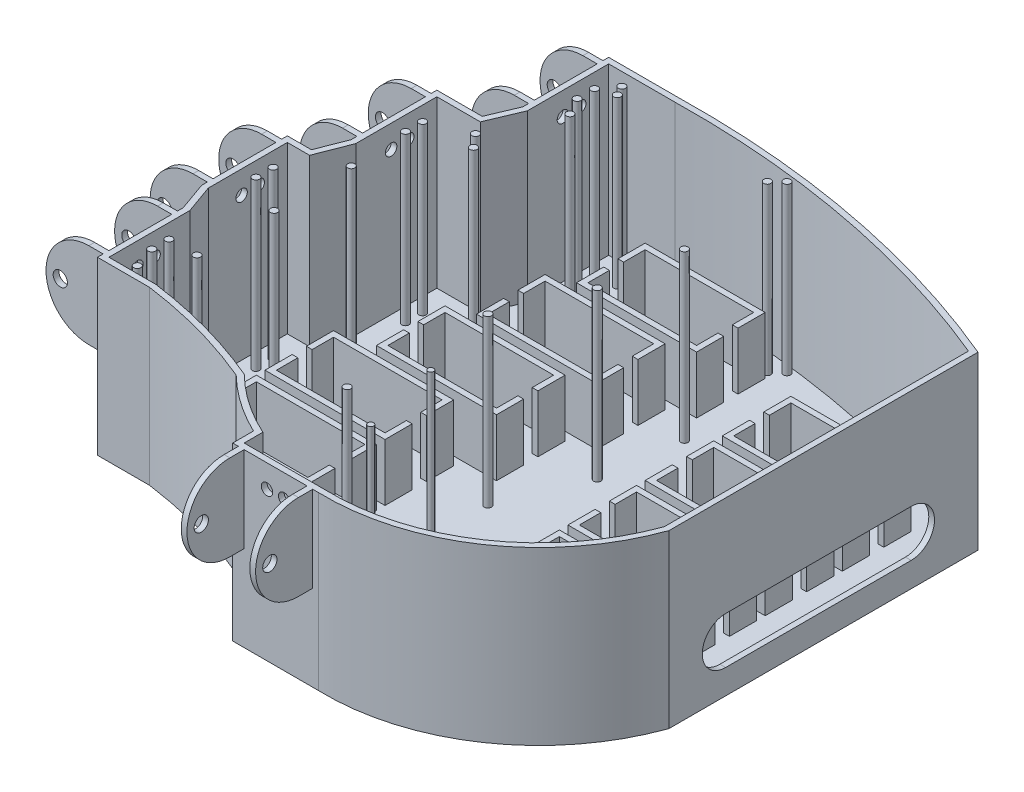
SolidWorks part; units mm, degrees
ref_plane "Front Plane" through (0, 0, 0) normal (0, 0, 1) x (1, 0, 0)
ref_plane "Top Plane" through (0, 0, 0) normal (0, 1, 0) x (1, 0, 0)
ref_plane "Right Plane" through (0, 0, 0) normal (1, 0, 0) x (0, 0, -1)
ref_plane "Palm Side Plane" through (0, 38.1, 0) normal (0, 1, 0) x (1, 0, 0)
ref_plane "Left Side Plane" through (0, 0, 63.5) normal (0, 0, 1) x (1, 0, 0)
ref_plane "Top Side Plane" through (-69.85, 0, 0) normal (1, 0, 0) x (0, 0, -1)
ref_plane "Wrist Plane" through (62.9138, 0, 0) normal (1, 0, 0) x (0, 0, -1)
sketch "Hand Direction Arrow" plane through (0, 38.1, 0) normal (0, 1, 0) x (1, 0, 0)
  line L0 (49.8191, -114.0829) -> (-36.738, -114.0829) construction
  line L1 (-36.738, -114.0829) -> (-22.4792, -131.555) construction
  line L2 (-36.738, -114.0829) -> (-22.4792, -99.8241) construction
sketch "Sketch2" plane through (0, 0, 0) normal (0, 1, 0) x (1, 0, 0)
  line L5 (-69.85, -63.5) -> (69.85, 63.5) construction
  line L6 (-69.85, 63.5) -> (69.85, -63.5) construction
  line L7 (-20.7784, 52.7587) -> (-36.189, 52.7587)
  line L8 (-36.189, 52.7587) -> (-36.189, 33.7087)
  line L9 (-42.9594, -42.4913) -> (-54.5039, -42.4913)
  line L10 (-54.5039, -42.4913) -> (-54.5039, -23.4413)
  line L11 (-54.5039, -23.4413) -> (-56.7676, -17.0913)
  line L12 (-51.4171, 1.9587) -> (-48.9477, 8.3087)
  line L14 (-56.7676, -17.0913) -> (-56.7676, 1.9587)
  line L15 (-56.7676, 1.9587) -> (-51.4171, 1.9587)
  line L16 (-38.8642, 27.3587) -> (-36.189, 33.7087)
  line L19 (15.3118, -63.2103) -> (-3.7382, -63.2103)
  line L20 (-3.7382, -63.2103) -> (-3.7382, -58.593)
  line L21 (61.5724, -31.5884) -> (61.5724, 37.0553)
  line L22 (-48.9477, 8.3087) -> (-48.9477, 27.3587)
  line L23 (-48.9477, 27.3587) -> (-38.8642, 27.3587)
  arc A0 (61.5724, 37.0553) -> (-20.7784, 52.7587) centre (-16.6219, -149.2259) ccw
  arc A2 (-42.9594, -42.4913) -> (-16.4221, -49.7553) centre (-56.8306, -145.2734) cw
  arc A3 (15.3118, -63.2103) -> (61.5724, -31.5884) centre (16.7508, -15.6666) ccw
  arc A5 (-3.7382, -58.593) -> (-16.4221, -49.7553) centre (16.7508, -15.6666) cw
  point P0 (0, 0)
  dimension "D1" = 19.05
  dimension "D2" = 19.05
  dimension "D3" = 19.05
  dimension "D4" = 19.05
  dimension "D5" = 19.05
  dimension "D6" = 6.35
  dimension "D7" = 6.35
extrude "Boss-Extrude1" add sketch "Sketch2" along normal blind 38.1
sketch "Sketch3" plane through (0, 38.1, 0) normal (0, 1, 0) x (1, 0, 0)
  line L5 (-68.58, -62.23) -> (68.58, 62.23) construction
  line L6 (-68.58, 62.23) -> (68.58, -62.23) construction
  line L7 (-20.1932, 51.4997) -> (-34.919, 51.4997)
  line L8 (-34.919, 51.4997) -> (-34.919, 33.4521)
  line L10 (-36.189, 52.7587) -> (-36.189, 33.7087) construction
  line L11 (-54.5039, -23.4413) -> (-54.5039, -42.4913) construction
  line L12 (-42.8744, -41.2213) -> (-53.2339, -41.2213)
  line L13 (-53.2339, -41.2213) -> (-53.2339, -23.2217)
  line L18 (-55.4976, -16.8717) -> (-55.4976, 0.6887)
  line L19 (-55.4976, 0.6887) -> (-50.5484, 0.6887)
  line L22 (-56.7676, 1.9587) -> (-56.7676, -17.0913) construction
  line L23 (-51.4171, 1.9587) -> (-56.7676, 1.9587) construction
  line L24 (-47.6777, 8.0704) -> (-47.6777, 26.0887)
  line L25 (-47.6777, 26.0887) -> (-38.0211, 26.0887)
  line L26 (-48.9477, 27.3587) -> (-48.9477, 8.3087) construction
  line L27 (-38.8642, 27.3587) -> (-48.9477, 27.3587) construction
  line L28 (-38.0211, 26.0887) -> (-34.919, 33.4521)
  line L29 (-36.189, 33.7087) -> (-38.8642, 27.3587) construction
  line L30 (-50.5484, 0.6887) -> (-47.6777, 8.0704)
  line L31 (-54.5039, -42.4913) -> (-42.9594, -42.4913) construction
  line L32 (-53.2339, -23.2217) -> (-55.4976, -16.8717)
  line L33 (-56.7676, -17.0913) -> (-54.5039, -23.4413) construction
  line L34 (-48.9477, 8.3087) -> (-51.4171, 1.9587) construction
  line L35 (15.3312, -61.9403) -> (-2.4682, -61.9403)
  line L36 (-2.4682, -61.9403) -> (-2.4682, -57.7843)
  line L37 (-3.7382, -58.593) -> (-3.7382, -63.2103) construction
  line L38 (-3.7382, -63.2103) -> (15.3118, -63.2103) construction
  line L39 (60.3024, -31.368) -> (60.3024, 36.2091)
  line L40 (61.5724, -31.5884) -> (61.5724, 37.0553) construction
  arc A1 (-20.1932, 51.4997) -> (60.3024, 36.2091) centre (-16.6219, -149.2259) cw
  arc A4 (61.5724, 37.0553) -> (-20.7784, 52.7587) centre (-16.6219, -149.2259) ccw construction
  arc A6 (-15.7053, -48.6798) -> (-2.4682, -57.7843) centre (16.7508, -15.6666) ccw
  arc A7 (15.3118, -63.2103) -> (61.5724, -31.5884) centre (16.7508, -15.6666) ccw construction
  arc A8 (-42.8744, -41.2213) -> (-15.7053, -48.6798) centre (-56.8306, -145.2734) cw
  arc A9 (-16.4221, -49.7553) -> (-42.9594, -42.4913) centre (-56.8306, -145.2734) ccw construction
  arc A11 (15.3118, -63.2103) -> (61.5724, -31.5884) centre (16.7508, -15.6666) ccw construction
  arc A12 (15.3312, -61.9403) -> (60.3024, -31.368) centre (16.7508, -15.6666) ccw
  point P0 (0, 0)
  point P6 (-45.5127, -25.7954)
  point P29 (-45.5127, -25.7954)
  point P52 (-54.0923, 1.9587)
  dimension "D2" = 1.27
  dimension "D3" = 1.27
  dimension "D5" = 1.27
  dimension "D6" = 1.27
  dimension "D8" = 1.27
  dimension "D4" = 1.27
  dimension "D7" = 1.27
  dimension "D9" = 1.27
  dimension "D10" = 1.27
  dimension "D11" = 1.27
  dimension "D12" = 1.27
  dimension "D13" = 1.27
  dimension "D14" = 1.27
  dimension "D15" = 1.27
  dimension "D16" = 1.27
  dimension "D17" = 1.27
extrude "Cut-Extrude1" cut sketch "Sketch3" against normal blind 36.83
sketch "Sketch6" plane through (0, 0, 0) normal (0, 1, 0) x (1, 0, 0)
  line L0 (-38.2959, -32.597) -> (-37.0259, -32.597)
  line L5 (-63.3937, -68.1577) -> (73.7663, 56.3023) construction
  line L6 (-64.5742, 57.9506) -> (72.5858, -66.5094) construction
  line L7 (-12.8959, -37.3595) -> (-37.0259, -37.3595)
  line L8 (-12.8959, -37.3595) -> (-12.8959, -32.597)
  line L9 (-12.8959, -24.6595) -> (-37.0259, -24.6595)
  line L10 (-37.0259, -37.3595) -> (-37.0259, -32.597)
  line L11 (-12.8959, -37.3595) -> (-37.0259, -24.6595) construction
  line L12 (-12.8959, -24.6595) -> (-37.0259, -37.3595) construction
  line L13 (-11.6259, -38.6295) -> (-38.2959, -38.6295)
  line L14 (-11.6259, -38.6295) -> (-11.6259, -32.597)
  line L15 (-11.6259, -23.3895) -> (-38.2959, -23.3895)
  line L16 (-38.2959, -38.6295) -> (-38.2959, -32.597)
  line L17 (-11.6259, -38.6295) -> (-38.2959, -23.3895) construction
  line L18 (-11.6259, -23.3895) -> (-38.2959, -38.6295) construction
  line L19 (-38.2959, -29.422) -> (-37.0259, -29.422)
  line L20 (-38.2959, -29.422) -> (-38.2959, -23.3895)
  line L21 (-37.0259, -29.422) -> (-37.0259, -24.6595)
  line L22 (-12.8959, -32.597) -> (-11.6259, -32.597)
  line L23 (-12.8959, -29.422) -> (-11.6259, -29.422)
  line L24 (-12.8959, -29.422) -> (-12.8959, -24.6595)
  line L25 (-11.6259, -29.422) -> (-11.6259, -23.3895)
  point P0 (5.5042, -5.6391)
  point P6 (-24.9609, -31.0095)
  point P29 (-24.9609, -31.0095)
  dimension "D6" = 1.27
  dimension "D7" = 1.27
  dimension "D9" = 12.7
  dimension "D10" = 24.13
  dimension "D11" = 4.7625
  dimension "D12" = 4.7625
  dimension "D13" = 4.7625
  dimension "D14" = 4.7625
extrude "Boss-Extrude2" add sketch "Sketch6" along normal blind 13.97
sketch "Sketch7" plane through (0, 0, 0) normal (0, 1, 0) x (1, 0, 0)
  line L0 (-38.2959, -15.452) -> (-37.0259, -15.452)
  line L5 (-11.6259, -23.3895) -> (-38.2959, -23.3895) construction
  line L6 (-38.2959, -23.3895) -> (-38.2959, -29.422) construction
  line L7 (-12.8959, -20.2145) -> (-37.0259, -20.2145)
  line L8 (-12.8959, -20.2145) -> (-12.8959, -15.452)
  line L9 (-12.8959, -7.5145) -> (-37.0259, -7.5145)
  line L10 (-37.0259, -20.2145) -> (-37.0259, -15.452)
  line L11 (-12.8959, -20.2145) -> (-37.0259, -7.5145) construction
  line L12 (-12.8959, -7.5145) -> (-37.0259, -20.2145) construction
  line L13 (-11.6259, -21.4845) -> (-38.2959, -21.4845)
  line L14 (-11.6259, -21.4845) -> (-11.6259, -15.452)
  line L15 (-11.6259, -6.2445) -> (-38.2959, -6.2445)
  line L16 (-38.2959, -21.4845) -> (-38.2959, -15.452)
  line L17 (-11.6259, -21.4845) -> (-38.2959, -6.2445) construction
  line L18 (-11.6259, -6.2445) -> (-38.2959, -21.4845) construction
  line L19 (-38.2959, -12.277) -> (-37.0259, -12.277)
  line L20 (-38.2959, -12.277) -> (-38.2959, -6.2445)
  line L21 (-37.0259, -12.277) -> (-37.0259, -7.5145)
  line L22 (-12.8959, -15.452) -> (-11.6259, -15.452)
  line L23 (-12.8959, -12.277) -> (-11.6259, -12.277)
  line L24 (-12.8959, -12.277) -> (-12.8959, -7.5145)
  line L25 (-11.6259, -12.277) -> (-11.6259, -6.2445)
  point P0 (-14.8998, -5.4903)
  point P6 (-24.9609, -13.8645)
  point P29 (-24.9609, -13.8645)
  dimension "D2" = 1.905
  dimension "D3" = 0
  dimension "D6" = 1.27
  dimension "D7" = 1.27
  dimension "D9" = 12.7
  dimension "D10" = 24.13
  dimension "D11" = 4.7625
  dimension "D12" = 4.7625
  dimension "D13" = 4.7625
  dimension "D14" = 4.7625
extrude "Boss-Extrude3" add sketch "Sketch7" along normal blind 13.97
sketch "Sketch15" plane through (0, 0, 0) normal (0, -1, 0) x (1, 0, 0)
  line L0 (-30.6759, -4.868) -> (-29.4059, -4.868)
  line L5 (-11.6259, 6.2445) -> (-38.2959, 6.2445) construction
  line L6 (-38.2959, 6.2445) -> (-38.2959, 12.277) construction
  line L7 (-5.2759, -9.6305) -> (-29.4059, -9.6305)
  line L8 (-5.2759, -9.6305) -> (-5.2759, -4.868)
  line L9 (-5.2759, 3.0695) -> (-29.4059, 3.0695)
  line L10 (-29.4059, -9.6305) -> (-29.4059, -4.868)
  line L11 (-5.2759, -9.6305) -> (-29.4059, 3.0695) construction
  line L12 (-5.2759, 3.0695) -> (-29.4059, -9.6305) construction
  line L13 (-4.0059, -10.9005) -> (-30.6759, -10.9005)
  line L14 (-4.0059, -10.9005) -> (-4.0059, -4.868)
  line L15 (-4.0059, 4.3395) -> (-30.6759, 4.3395)
  line L16 (-30.6759, -10.9005) -> (-30.6759, -4.868)
  line L17 (-4.0059, -10.9005) -> (-30.6759, 4.3395) construction
  line L18 (-4.0059, 4.3395) -> (-30.6759, -10.9005) construction
  line L19 (-30.6759, -1.693) -> (-29.4059, -1.693)
  line L20 (-30.6759, -1.693) -> (-30.6759, 4.3395)
  line L21 (-29.4059, -1.693) -> (-29.4059, 3.0695)
  line L22 (-5.2759, -4.868) -> (-4.0059, -4.868)
  line L23 (-5.2759, -1.693) -> (-4.0059, -1.693)
  line L24 (-5.2759, -1.693) -> (-5.2759, 3.0695)
  line L25 (-4.0059, -1.693) -> (-4.0059, 4.3395)
  point P0 (-6.5637, 8.998)
  point P6 (-17.3409, -3.2805)
  point P29 (-17.3409, -3.2805)
  dimension "D2" = 1.905
  dimension "D3" = 7.62
  dimension "D6" = 1.27
  dimension "D7" = 1.27
  dimension "D9" = 12.7
  dimension "D10" = 24.13
  dimension "D11" = 4.7625
  dimension "D12" = 4.7625
  dimension "D13" = 4.7625
  dimension "D14" = 4.7625
extrude "Boss-Extrude4" add sketch "Sketch15" against normal blind 13.97
sketch "Sketch16" plane through (0, 0, 0) normal (0, -1, 0) x (1, 0, 0)
  line L0 (-25.5959, -22.013) -> (-24.3259, -22.013)
  line L5 (-30.6759, -10.9005) -> (-4.0059, -10.9005) construction
  line L6 (-30.6759, -4.868) -> (-30.6759, -10.9005) construction
  line L7 (-0.1959, -26.7755) -> (-24.3259, -26.7755)
  line L8 (-0.1959, -26.7755) -> (-0.1959, -22.013)
  line L9 (-0.1959, -14.0755) -> (-24.3259, -14.0755)
  line L10 (-24.3259, -26.7755) -> (-24.3259, -22.013)
  line L11 (-0.1959, -26.7755) -> (-24.3259, -14.0755) construction
  line L12 (-0.1959, -14.0755) -> (-24.3259, -26.7755) construction
  line L13 (1.0741, -28.0455) -> (-25.5959, -28.0455)
  line L14 (1.0741, -28.0455) -> (1.0741, -22.013)
  line L15 (1.0741, -12.8055) -> (-25.5959, -12.8055)
  line L16 (-25.5959, -28.0455) -> (-25.5959, -22.013)
  line L17 (1.0741, -28.0455) -> (-25.5959, -12.8055) construction
  line L18 (1.0741, -12.8055) -> (-25.5959, -28.0455) construction
  line L19 (-25.5959, -18.838) -> (-24.3259, -18.838)
  line L20 (-25.5959, -18.838) -> (-25.5959, -12.8055)
  line L21 (-24.3259, -18.838) -> (-24.3259, -14.0755)
  line L22 (-0.1959, -22.013) -> (1.0741, -22.013)
  line L23 (-0.1959, -18.838) -> (1.0741, -18.838)
  line L24 (-0.1959, -18.838) -> (-0.1959, -14.0755)
  line L25 (1.0741, -18.838) -> (1.0741, -12.8055)
  point P0 (1.9027, -6.9539)
  point P6 (-12.2609, -20.4255)
  point P29 (-12.2609, -20.4255)
  dimension "D2" = 1.905
  dimension "D3" = 5.08
  dimension "D6" = 1.27
  dimension "D7" = 1.27
  dimension "D9" = 12.7
  dimension "D10" = 24.13
  dimension "D11" = 4.7625
  dimension "D12" = 4.7625
  dimension "D13" = 4.7625
  dimension "D14" = 4.7625
extrude "Boss-Extrude5" add sketch "Sketch16" against normal blind 13.97
sketch "Sketch17" plane through (0, 0, 0) normal (0, -1, 0) x (1, 0, 0)
  line L0 (-20.5159, -39.158) -> (-19.2459, -39.158)
  line L5 (-25.5959, -28.0455) -> (1.0741, -28.0455) construction
  line L6 (-25.5959, -22.013) -> (-25.5959, -28.0455) construction
  line L7 (4.8841, -43.9205) -> (-19.2459, -43.9205)
  line L8 (4.8841, -43.9205) -> (4.8841, -39.158)
  line L9 (4.8841, -31.2205) -> (-19.2459, -31.2205)
  line L10 (-19.2459, -43.9205) -> (-19.2459, -39.158)
  line L11 (4.8841, -43.9205) -> (-19.2459, -31.2205) construction
  line L12 (4.8841, -31.2205) -> (-19.2459, -43.9205) construction
  line L13 (6.1541, -45.1905) -> (-20.5159, -45.1905)
  line L14 (6.1541, -45.1905) -> (6.1541, -39.158)
  line L15 (6.1541, -29.9505) -> (-20.5159, -29.9505)
  line L16 (-20.5159, -45.1905) -> (-20.5159, -39.158)
  line L17 (6.1541, -45.1905) -> (-20.5159, -29.9505) construction
  line L18 (6.1541, -29.9505) -> (-20.5159, -45.1905) construction
  line L19 (-20.5159, -35.983) -> (-19.2459, -35.983)
  line L20 (-20.5159, -35.983) -> (-20.5159, -29.9505)
  line L21 (-19.2459, -35.983) -> (-19.2459, -31.2205)
  line L22 (4.8841, -39.158) -> (6.1541, -39.158)
  line L23 (4.8841, -35.983) -> (6.1541, -35.983)
  line L24 (4.8841, -35.983) -> (4.8841, -31.2205)
  line L25 (6.1541, -35.983) -> (6.1541, -29.9505)
  point P0 (6.1079, -24.4951)
  point P6 (-7.1809, -37.5705)
  point P29 (-7.1809, -37.5705)
  dimension "D2" = 1.905
  dimension "D3" = 5.08
  dimension "D6" = 1.27
  dimension "D7" = 1.27
  dimension "D9" = 12.7
  dimension "D10" = 24.13
  dimension "D11" = 4.7625
  dimension "D12" = 4.7625
  dimension "D13" = 4.7625
  dimension "D14" = 4.7625
extrude "Boss-Extrude6" add sketch "Sketch17" against normal blind 13.97
sketch "Sketch18" plane through (0, 0, 0) normal (0, -1, 0) x (1, 0, 0)
  line L0 (14.981, 42.6949) -> (16.251, 42.6949)
  line L7 (40.381, 37.9324) -> (16.251, 37.9324)
  line L8 (40.381, 37.9324) -> (40.381, 42.6949)
  line L9 (40.381, 50.6324) -> (16.251, 50.6324)
  line L10 (16.251, 37.9324) -> (16.251, 42.6949)
  line L11 (40.381, 37.9324) -> (16.251, 50.6324) construction
  line L12 (40.381, 50.6324) -> (16.251, 37.9324) construction
  line L13 (41.651, 36.6624) -> (14.981, 36.6624)
  line L14 (41.651, 36.6624) -> (41.651, 42.6949)
  line L15 (41.651, 51.9024) -> (14.981, 51.9024)
  line L16 (14.981, 36.6624) -> (14.981, 42.6949)
  line L17 (41.651, 36.6624) -> (14.981, 51.9024) construction
  line L18 (41.651, 51.9024) -> (14.981, 36.6624) construction
  line L19 (14.981, 45.8699) -> (16.251, 45.8699)
  line L20 (14.981, 45.8699) -> (14.981, 51.9024)
  line L21 (16.251, 45.8699) -> (16.251, 50.6324)
  line L22 (40.381, 42.6949) -> (41.651, 42.6949)
  line L23 (40.381, 45.8699) -> (41.651, 45.8699)
  line L24 (40.381, 45.8699) -> (40.381, 50.6324)
  line L25 (41.651, 45.8699) -> (41.651, 51.9024)
  point P0 (43.5107, 54.1626)
  point P6 (28.316, 44.2824)
  point P29 (28.316, 44.2824)
  dimension "D6" = 1.27
  dimension "D7" = 1.27
  dimension "D9" = 12.7
  dimension "D10" = 24.13
  dimension "D11" = 4.7625
  dimension "D12" = 4.7625
  dimension "D13" = 4.7625
  dimension "D14" = 4.7625
extrude "Boss-Extrude7" add sketch "Sketch18" against normal blind 13.97
sketch "Sketch19" plane through (0, 0, 0) normal (0, -1, 0) x (1, 0, 0)
  line L0 (25.141, 25.5499) -> (26.411, 25.5499)
  line L5 (14.981, 36.6624) -> (41.651, 36.6624) construction
  line L6 (14.981, 42.6949) -> (14.981, 36.6624) construction
  line L7 (50.541, 20.7874) -> (26.411, 20.7874)
  line L8 (50.541, 20.7874) -> (50.541, 25.5499)
  line L9 (50.541, 33.4874) -> (26.411, 33.4874)
  line L10 (26.411, 20.7874) -> (26.411, 25.5499)
  line L11 (50.541, 20.7874) -> (26.411, 33.4874) construction
  line L12 (50.541, 33.4874) -> (26.411, 20.7874) construction
  line L13 (51.811, 19.5174) -> (25.141, 19.5174)
  line L14 (51.811, 19.5174) -> (51.811, 25.5499)
  line L15 (51.811, 34.7574) -> (25.141, 34.7574)
  line L16 (25.141, 19.5174) -> (25.141, 25.5499)
  line L17 (51.811, 19.5174) -> (25.141, 34.7574) construction
  line L18 (51.811, 34.7574) -> (25.141, 19.5174) construction
  line L19 (25.141, 28.7249) -> (26.411, 28.7249)
  line L20 (25.141, 28.7249) -> (25.141, 34.7574)
  line L21 (26.411, 28.7249) -> (26.411, 33.4874)
  line L22 (50.541, 25.5499) -> (51.811, 25.5499)
  line L23 (50.541, 28.7249) -> (51.811, 28.7249)
  line L24 (50.541, 28.7249) -> (50.541, 33.4874)
  line L25 (51.811, 28.7249) -> (51.811, 34.7574)
  point P0 (52.4146, 37.8023)
  point P6 (38.476, 27.1374)
  point P29 (38.476, 27.1374)
  dimension "D2" = 1.905
  dimension "D3" = 10.16
  dimension "D6" = 1.27
  dimension "D7" = 1.27
  dimension "D9" = 12.7
  dimension "D10" = 24.13
  dimension "D11" = 4.7625
  dimension "D12" = 4.7625
  dimension "D13" = 4.7625
  dimension "D14" = 4.7625
extrude "Boss-Extrude8" add sketch "Sketch19" against normal blind 13.97
sketch "Sketch20" plane through (0, 0, 0) normal (0, -1, 0) x (1, 0, 0)
  line L0 (25.141, 8.4049) -> (26.411, 8.4049)
  line L5 (25.141, 25.5499) -> (25.141, 19.5174) construction
  line L6 (25.141, 19.5174) -> (51.811, 19.5174) construction
  line L7 (50.541, 3.6424) -> (26.411, 3.6424)
  line L8 (50.541, 3.6424) -> (50.541, 8.4049)
  line L9 (50.541, 16.3424) -> (26.411, 16.3424)
  line L10 (26.411, 3.6424) -> (26.411, 8.4049)
  line L11 (50.541, 3.6424) -> (26.411, 16.3424) construction
  line L12 (50.541, 16.3424) -> (26.411, 3.6424) construction
  line L13 (51.811, 2.3724) -> (25.141, 2.3724)
  line L14 (51.811, 2.3724) -> (51.811, 8.4049)
  line L15 (51.811, 17.6124) -> (25.141, 17.6124)
  line L16 (25.141, 2.3724) -> (25.141, 8.4049)
  line L17 (51.811, 2.3724) -> (25.141, 17.6124) construction
  line L18 (51.811, 17.6124) -> (25.141, 2.3724) construction
  line L19 (25.141, 11.5799) -> (26.411, 11.5799)
  line L20 (25.141, 11.5799) -> (25.141, 17.6124)
  line L21 (26.411, 11.5799) -> (26.411, 16.3424)
  line L22 (50.541, 8.4049) -> (51.811, 8.4049)
  line L23 (50.541, 11.5799) -> (51.811, 11.5799)
  line L24 (50.541, 11.5799) -> (50.541, 16.3424)
  line L25 (51.811, 11.5799) -> (51.811, 17.6124)
  point P0 (54.8865, 20.8211)
  point P6 (38.476, 9.9924)
  point P29 (38.476, 9.9924)
  dimension "D2" = 0
  dimension "D3" = 1.905
  dimension "D6" = 1.27
  dimension "D7" = 1.27
  dimension "D9" = 12.7
  dimension "D10" = 24.13
  dimension "D11" = 4.7625
  dimension "D12" = 4.7625
  dimension "D13" = 4.7625
  dimension "D14" = 4.7625
extrude "Boss-Extrude9" add sketch "Sketch20" against normal blind 13.97
sketch "Sketch21" plane through (0, 0, 0) normal (0, -1, 0) x (1, 0, 0)
  line L0 (25.141, -8.7401) -> (26.411, -8.7401)
  line L5 (25.141, 2.3724) -> (51.811, 2.3724) construction
  line L6 (25.141, 8.4049) -> (25.141, 2.3724) construction
  line L7 (50.541, -13.5026) -> (26.411, -13.5026)
  line L8 (50.541, -13.5026) -> (50.541, -8.7401)
  line L9 (50.541, -0.8026) -> (26.411, -0.8026)
  line L10 (26.411, -13.5026) -> (26.411, -8.7401)
  line L11 (50.541, -13.5026) -> (26.411, -0.8026) construction
  line L12 (50.541, -0.8026) -> (26.411, -13.5026) construction
  line L13 (51.811, -14.7726) -> (25.141, -14.7726)
  line L14 (51.811, -14.7726) -> (51.811, -8.7401)
  line L15 (51.811, 0.4674) -> (25.141, 0.4674)
  line L16 (25.141, -14.7726) -> (25.141, -8.7401)
  line L17 (51.811, -14.7726) -> (25.141, 0.4674) construction
  line L18 (51.811, 0.4674) -> (25.141, -14.7726) construction
  line L19 (25.141, -5.5651) -> (26.411, -5.5651)
  line L20 (25.141, -5.5651) -> (25.141, 0.4674)
  line L21 (26.411, -5.5651) -> (26.411, -0.8026)
  line L22 (50.541, -8.7401) -> (51.811, -8.7401)
  line L23 (50.541, -5.5651) -> (51.811, -5.5651)
  line L24 (50.541, -5.5651) -> (50.541, -0.8026)
  line L25 (51.811, -5.5651) -> (51.811, 0.4674)
  point P0 (52.1156, 3.8173)
  point P6 (38.476, -7.1526)
  point P29 (38.476, -7.1526)
  dimension "D2" = 1.905
  dimension "D3" = 0
  dimension "D6" = 1.27
  dimension "D7" = 1.27
  dimension "D9" = 12.7
  dimension "D10" = 24.13
  dimension "D11" = 4.7625
  dimension "D12" = 4.7625
  dimension "D13" = 4.7625
  dimension "D14" = 4.7625
extrude "Boss-Extrude10" add sketch "Sketch21" against normal blind 13.97
sketch "Sketch22" plane through (0, 0, 0) normal (0, -1, 0) x (1, 0, 0)
  line L0 (25.141, -25.8851) -> (26.411, -25.8851)
  line L5 (25.141, -14.7726) -> (51.811, -14.7726) construction
  line L6 (25.141, -8.7401) -> (25.141, -14.7726) construction
  line L7 (50.541, -30.6476) -> (26.411, -30.6476)
  line L8 (50.541, -30.6476) -> (50.541, -25.8851)
  line L9 (50.541, -17.9476) -> (26.411, -17.9476)
  line L10 (26.411, -30.6476) -> (26.411, -25.8851)
  line L11 (50.541, -30.6476) -> (26.411, -17.9476) construction
  line L12 (50.541, -17.9476) -> (26.411, -30.6476) construction
  line L13 (51.811, -31.9176) -> (25.141, -31.9176)
  line L14 (51.811, -31.9176) -> (51.811, -25.8851)
  line L15 (51.811, -16.6776) -> (25.141, -16.6776)
  line L16 (25.141, -31.9176) -> (25.141, -25.8851)
  line L17 (51.811, -31.9176) -> (25.141, -16.6776) construction
  line L18 (51.811, -16.6776) -> (25.141, -31.9176) construction
  line L19 (25.141, -22.7101) -> (26.411, -22.7101)
  line L20 (25.141, -22.7101) -> (25.141, -16.6776)
  line L21 (26.411, -22.7101) -> (26.411, -17.9476)
  line L22 (50.541, -25.8851) -> (51.811, -25.8851)
  line L23 (50.541, -22.7101) -> (51.811, -22.7101)
  line L24 (50.541, -22.7101) -> (50.541, -17.9476)
  line L25 (51.811, -22.7101) -> (51.811, -16.6776)
  point P0 (57.6091, -14.277)
  point P6 (38.476, -24.2976)
  point P29 (38.476, -24.2976)
  dimension "D2" = 1.905
  dimension "D3" = 0
  dimension "D6" = 1.27
  dimension "D7" = 1.27
  dimension "D9" = 12.7
  dimension "D10" = 24.13
  dimension "D11" = 4.7625
  dimension "D12" = 4.7625
  dimension "D13" = 4.7625
  dimension "D14" = 4.7625
extrude "Boss-Extrude11" add sketch "Sketch22" against normal blind 13.97
sketch "Sketch25" plane through (0, 0, 63.5) normal (0, 0, 1) x (1, 0, 0)
  line L1 (49.8191, 38.1) -> (-36.738, 38.1) construction
  line L6 (-3.7382, 38.1) -> (-3.7382, 0) construction
  line L7 (15.3118, 38.1) -> (15.3118, 0) construction
  circle A0 centre (7.6918, 33.02) radius 1.27
  circle A1 centre (3.8818, 33.02) radius 1.27
  dimension "D3" = 7.62
  dimension "D1" = 5.08
  dimension "D2" = 5.08
  dimension "D4" = 7.62
extrude "Thumb Holes" cut sketch "Sketch25" against normal blind 12.7
sketch "Sketch31" plane through (-69.85, 0, 0) normal (1, 0, 0) x (0, 0, -1)
  line L0 (-23.4413, 38.1) -> (-23.4413, 0) construction
  line L1 (-23.4413, 38.1) -> (-42.4913, 38.1) construction
  line L2 (-42.4913, 38.1) -> (-42.4913, 0) construction
  circle A0 centre (-31.0613, 33.02) radius 1.27
  circle A1 centre (-34.8713, 33.02) radius 1.27
  dimension "D1" = 7.62
  dimension "D2" = 5.08
  dimension "D3" = 5.08
  dimension "D4" = 7.62
extrude "Index Finger Holes" cut sketch "Sketch31" along normal blind 17.018
sketch "Sketch32" plane through (-69.85, 0, 0) normal (1, 0, 0) x (0, 0, -1)
  line L0 (1.9587, 38.1) -> (1.9587, 0) construction
  line L1 (-17.0913, 38.1) -> (-17.0913, 0) construction
  line L2 (1.9587, 38.1) -> (-17.0913, 38.1) construction
  circle A0 centre (-9.4713, 33.02) radius 1.27
  circle A1 centre (-5.6613, 33.02) radius 1.27
  dimension "D1" = 7.62
  dimension "D2" = 7.62
  dimension "D3" = 5.08
  dimension "D4" = 5.08
extrude "Middle Finger Holes" cut sketch "Sketch32" along normal blind 15.24
sketch "Sketch33" plane through (-69.85, 0, 0) normal (1, 0, 0) x (0, 0, -1)
  line L0 (27.3587, 38.1) -> (27.3587, 0) construction
  line L1 (27.3587, 38.1) -> (8.3087, 38.1) construction
  line L2 (8.3087, 38.1) -> (8.3087, 0) construction
  circle A0 centre (15.9287, 33.02) radius 1.27
  circle A1 centre (19.7387, 33.02) radius 1.27
  dimension "D1" = 7.62
  dimension "D2" = 5.08
  dimension "D3" = 5.08
  dimension "D4" = 7.62
extrude "Ring Finger Holes" cut sketch "Sketch33" along normal blind 22.86
sketch "Sketch34" plane through (-69.85, 0, 0) normal (1, 0, 0) x (0, 0, -1)
  line L0 (52.7587, 38.1) -> (33.7087, 38.1) construction
  line L1 (52.8014, 0) -> (52.8014, 38.1) construction
  line L2 (33.7087, 38.1) -> (33.7087, 0) construction
  circle A0 centre (41.3287, 33.02) radius 1.27
  circle A1 centre (45.1814, 33.02) radius 1.27
  dimension "D1" = 5.08
  dimension "D2" = 7.62
  dimension "D3" = 7.62
  dimension "D4" = 5.08
extrude "Pinky Finger Holes" cut sketch "Sketch34" along normal blind 35.56
sketch "Sketch26" plane through (0, 38.1, 0) normal (0, 1, 0) x (1, 0, 0)
  line L0 (-1.8504, -40.4696) -> (-48.4714, -40.4696) construction
  line L1 (8.3049, 24.2976) -> (8.3049, 48.6758) construction
  line L2 (6.0975, 7.1526) -> (6.0975, 46.5196) construction
  line L3 (-1.0566, -9.9924) -> (-1.0566, -39.6758) construction
  line L4 (-53.2339, -23.2217) -> (-53.2339, -41.2213) construction
  line L5 (-37.0259, -15.452) -> (-38.2959, -15.452) construction
  line L6 (14.981, -45.8699) -> (16.251, -45.8699) construction
  line L7 (25.141, -28.7249) -> (26.411, -28.7249) construction
  line L8 (25.141, -11.5799) -> (26.411, -11.5799) construction
  line L9 (25.141, 5.5651) -> (26.411, 5.5651) construction
  line L10 (25.141, 22.7101) -> (26.411, 22.7101) construction
  line L11 (-30.6759, 1.693) -> (-29.4059, 1.693) construction
  line L12 (-25.5959, 18.838) -> (-24.3259, 18.838) construction
  line L13 (-20.5159, 35.983) -> (-19.2459, 35.983) construction
  line L14 (5.3037, 47.3134) -> (-28.0099, 47.3134) construction
  line L15 (7.5112, 49.4695) -> (-29.1533, 49.4695) construction
  line L16 (-53.2339, -23.2217) -> (-53.2339, -41.2213) construction
  line L17 (-55.4976, 0.6887) -> (-55.4976, -16.8717) construction
  line L18 (-47.6777, 26.0887) -> (-47.6777, 8.0704) construction
  line L19 (-47.6777, 26.0887) -> (-47.6777, 8.0704) construction
  line L20 (-34.919, 51.4997) -> (-34.919, 33.4521) construction
  line L21 (-34.919, 51.4997) -> (-34.919, 33.4521) construction
  line L22 (-37.0259, -32.597) -> (-38.2959, -32.597) construction
  line L23 (-49.2652, -39.6758) -> (-49.2652, -34.8713) construction
  circle A0 centre (8.0093, -44.2824) radius 0.635
  circle A1 centre (4.1993, -27.1374) radius 0.635
  circle A2 centre (-0.2629, -9.9924) radius 0.7937
  circle A3 centre (6.8912, 7.1526) radius 0.7938
  circle A4 centre (9.0987, 24.2976) radius 0.7937
  circle A5 centre (-1.8504, -39.6758) radius 0.7937
  circle A6 centre (7.5112, 48.6758) radius 0.7938
  circle A7 centre (5.3037, 46.5196) radius 0.7938
  circle A8 centre (-48.4714, -39.6758) radius 0.7937
  circle A9 centre (-52.3226, -9.4713) radius 0.7937
  circle A10 centre (-52.3226, -5.6613) radius 0.7937
  circle A11 centre (-43.8931, -13.8645) radius 0.7937
  circle A12 centre (-43.8931, 3.2805) radius 0.7937
  circle A13 centre (-33.8741, 20.4255) radius 0.7937
  circle A14 centre (-44.5027, 15.9287) radius 0.7937
  circle A15 centre (-29.6038, 37.5705) radius 0.7937
  circle A16 centre (-36.3066, 23.2954) radius 0.7937
  circle A17 centre (-44.5027, 19.7387) radius 0.7937
  circle A18 centre (-28.0099, 46.5196) radius 0.7937
  circle A19 centre (-29.1533, 48.6758) radius 0.7937
  circle A20 centre (-31.744, 41.3287) radius 0.7937
  circle A21 centre (-31.744, 45.1814) radius 0.7937
  circle A22 centre (-50.0589, -34.8713) radius 0.7937
  circle A23 centre (-50.0589, -31.0613) radius 0.7937
  circle A24 centre (-43.8931, -31.0095) radius 0.7937
  point P80 (-36.3066, 23.2954)
  point P81 (-43.8931, -31.0613)
  point P108 (-43.8931, -13.8645)
  point P109 (-43.8931, 3.2805)
  dimension "D7" = 1.27
  dimension "D14" = 1.5875
  dimension "D15" = 1.5875
  dimension "D16" = 1.5875
  dimension "D17" = 1.5875
  dimension "D18" = 1.5875
  dimension "D19" = 1.5875
  dimension "D20" = 1.5875
  dimension "D21" = 1.5875
  dimension "D22" = 1.5875
  dimension "D23" = 1.5875
  dimension "D24" = 1.5875
  dimension "D25" = 1.5875
  dimension "D26" = 1.5875
  dimension "D27" = 1.5875
  dimension "D28" = 1.5875
  dimension "D29" = 1.5875
  dimension "D30" = 1.5875
  dimension "D31" = 1.5875
  dimension "D32" = 1.5875
  dimension "D33" = 1.5875
  dimension "D34" = 1.5875
  dimension "D35" = 1.5875
  dimension "D41" = 1.27
  dimension "D52" = 1.5875
  dimension "D1" = 1.5875
  dimension "D2" = 1.5875
  dimension "D3" = 1.5875
  dimension "D4" = 1.5875
  dimension "D5" = 1.5875
  dimension "D8" = 1.5875
  dimension "D9" = 1.5875
  dimension "D10" = 1.5875
  dimension "D11" = 1.5875
  dimension "D12" = 1.5875
  dimension "D13" = 1.5875
  dimension "D36" = 1.27
  dimension "D37" = 1.27
  dimension "D38" = 1.27
  dimension "D39" = 1.27
  dimension "D40" = 1.27
  dimension "D42" = 1.27
  dimension "D43" = 3.175
  dimension "D44" = 3.175
  dimension "D45" = 3.175
  dimension "D46" = 3.175
  dimension "D47" = 3.175
  dimension "D48" = 3.175
  dimension "D49" = 3.175
  dimension "D50" = 3.175
  dimension "D51" = 1.5875
extrude "Guide Poles" add sketch "Sketch26" against normal blind 36.83
ref_plane "Pinky Attachment Plane" through (0, 0, -52.7587) normal (0, 0, -1) x (-1, 0, 0)
ref_plane "Ring Attachment Plane" through (0, 0, -27.3587) normal (0, 0, -1) x (-1, 0, 0)
ref_plane "Middle Attachment Plane" through (0, 0, -1.9587) normal (0, 0, -1) x (-1, 0, 0)
ref_plane "Pointer Attachment Plane" through (0, 0, 23.4413) normal (0, 0, -1) x (-1, 0, 0)
ref_plane "Thumb Attachment Plane" through (-3.7382, 0, 0) normal (-1, 0, 0) x (0, 0, 1)
sketch "Sketch35" plane through (0, 0, -52.7587) normal (0, 0, -1) x (-1, 0, 0)
  line L0 (36.189, 38.1) -> (39.364, 38.1)
  line L1 (36.189, 38.1) -> (36.189, 0) construction
  line L2 (38.8642, 38.1) -> (48.9477, 38.1) construction
  line L3 (36.189, 19.05) -> (39.364, 19.05)
  line L4 (39.364, 38.1) -> (39.364, 19.05) construction
  line L5 (36.189, 38.1) -> (36.189, 19.05)
  circle A1 centre (45.714, 28.575) radius 1.5875
  arc A2 (39.364, 38.1) -> (39.364, 19.05) centre (39.364, 28.575) cw
  dimension "D1" = 9.525
  dimension "D2" = 3.175
extrude "Pinky Attachment" add sketch "Sketch35" against normal blind 19.05
sketch "Sketch36" plane through (0, 0, -27.3587) normal (0, 0, -1) x (-1, 0, 0)
  line L2 (52.1227, 38.1) -> (48.9477, 38.1)
  line L3 (48.9477, 38.1) -> (48.9477, 19.05)
  line L4 (48.9477, 38.1) -> (48.9477, 0) construction
  line L5 (48.9477, 19.05) -> (52.1227, 19.05)
  line L6 (52.1227, 38.1) -> (52.1227, 19.05) construction
  arc A0 (52.1227, 38.1) -> (52.1227, 19.05) centre (52.1227, 28.575) cw
  circle A1 centre (58.4727, 28.7074) radius 1.5875
  dimension "D1" = 3.175
  dimension "D2" = 9.525
extrude "Ring Attachment" add sketch "Sketch36" against normal blind 19.05
sketch "Sketch37" plane through (0, 0, -1.9587) normal (0, 0, -1) x (-1, 0, 0)
  line L2 (56.7676, 38.1) -> (56.7676, 19.05)
  line L3 (56.7676, 38.1) -> (56.7676, 0) construction
  line L4 (56.7676, 19.05) -> (59.9426, 19.05)
  line L6 (59.9426, 38.1) -> (56.7676, 38.1)
  line L7 (59.9426, 38.1) -> (59.9426, 19.05) construction
  arc A2 (59.9426, 38.1) -> (59.9426, 19.05) centre (59.9426, 28.575) cw
  circle A3 centre (66.2926, 28.575) radius 1.5875
  dimension "D1" = 3.175
  dimension "D2" = 9.525
  dimension "D3" = 9.525
extrude "Middle Attachment" add sketch "Sketch37" against normal blind 19.05
sketch "Sketch38" plane through (0, 0, 23.4413) normal (0, 0, -1) x (-1, 0, 0)
  line L2 (54.5039, 38.1) -> (57.6789, 38.1)
  line L3 (57.6789, 38.1) -> (57.6789, 19.05) construction
  line L4 (57.6789, 19.05) -> (54.5039, 19.05)
  line L5 (54.5039, 38.1) -> (54.5039, 0) construction
  line L6 (54.5039, 38.1) -> (54.5039, 0) construction
  line L7 (54.5039, 38.1) -> (54.5039, 19.05)
  arc A2 (57.6789, 38.1) -> (57.6789, 19.05) centre (57.6789, 28.575) cw
  circle A3 centre (64.0289, 28.575) radius 1.5875
  dimension "D1" = 3.175
  dimension "D2" = 9.525
extrude "Pointer Attachment" add sketch "Sketch38" against normal blind 19.05
sketch "Sketch39" plane through (-3.7382, 0, 0) normal (-1, 0, 0) x (0, 0, 1)
  line L1 (63.2103, 38.1) -> (66.3853, 38.1)
  line L4 (63.2103, 19.05) -> (66.3853, 19.05)
  line L5 (63.2103, 38.1) -> (63.2103, 0) construction
  line L6 (63.2103, 38.1) -> (63.2103, 19.05)
  line L7 (66.3853, 38.1) -> (66.3853, 19.05) construction
  arc A0 (66.3853, 38.1) -> (66.3853, 19.05) centre (66.3853, 28.575) cw
  circle A1 centre (72.7353, 28.575) radius 1.5875
  dimension "D1" = 3.175
  dimension "D2" = 9.525
extrude "Thumb Attachment" add sketch "Sketch39" against normal blind 19.05
sketch "Sketch40" plane through (0, 38.1, 0) normal (0, 1, 0) x (1, 0, 0)
  line L1 (-1.1982, -63.2103) -> (12.7718, -63.2103)
  line L2 (-1.1982, -63.2103) -> (-1.1982, -76.444)
  line L4 (12.7718, -63.2103) -> (12.7718, -77.4264)
  line L5 (-2.4682, -63.2103) -> (-2.4682, -76.444)
  line L6 (-2.4682, -76.444) -> (-1.1982, -76.444)
  line L7 (-6.4204, -63.2103) -> (-2.4682, -63.2103)
  line L8 (15.3118, -63.2103) -> (14.0418, -63.2103)
  line L9 (14.0418, -63.2103) -> (14.0418, -77.4264)
  line L10 (14.0418, -77.4264) -> (12.7718, -77.4264)
  line L11 (-54.5039, -42.4913) -> (-54.5039, -41.2213)
  line L13 (-54.5039, -41.2213) -> (-67.8581, -41.2213)
  line L15 (-67.8581, -41.2213) -> (-67.8581, -39.9513)
  line L16 (-67.8581, -39.9513) -> (-54.5039, -39.9513)
  line L17 (-54.5039, -39.9513) -> (-54.5039, -25.9813)
  line L18 (-54.5039, -25.9813) -> (-68.6555, -25.9813)
  line L19 (-68.6555, -25.9813) -> (-68.6555, -24.7113)
  line L20 (-68.6555, -24.7113) -> (-54.5039, -24.7113)
  line L21 (-54.5039, -24.7113) -> (-54.5039, -23.4413)
  line L22 (-56.7676, -17.0913) -> (-56.7676, -15.8213)
  line L24 (-56.7676, -15.8213) -> (-70.3975, -15.8213)
  line L25 (-70.3975, -15.8213) -> (-70.3975, -14.5513)
  line L26 (-70.3975, -14.5513) -> (-56.7676, -14.5513)
  line L27 (-56.7676, -14.5513) -> (-56.7676, -0.5813)
  line L28 (-56.7676, -0.5813) -> (-71.3004, -0.5813)
  line L29 (-71.3004, -0.5813) -> (-71.3004, 0.6887)
  line L31 (-56.7676, 0.6887) -> (-56.7676, 1.9587)
  line L32 (-71.3004, 0.6887) -> (-56.7676, 0.6887)
  line L33 (-47.6777, 26.0887) -> (-47.6777, 8.0704) construction
  line L34 (-48.9477, 8.3087) -> (-48.9477, 9.5787)
  line L36 (-48.9477, 9.5787) -> (-62.605, 9.5787)
  line L37 (-62.605, 9.5787) -> (-62.605, 10.8487)
  line L38 (-62.605, 10.8487) -> (-48.9477, 10.8487)
  line L39 (-48.9477, 10.8487) -> (-48.9477, 24.8187)
  line L40 (-48.9477, 24.8187) -> (-63.0911, 24.8187)
  line L41 (-63.0911, 24.8187) -> (-63.0911, 26.0887)
  line L42 (-63.0911, 26.0887) -> (-48.9477, 26.0887)
  line L43 (-48.9477, 26.0887) -> (-48.9477, 27.3587)
  line L44 (-36.189, 33.7087) -> (-36.189, 34.9787)
  line L45 (-2.4682, -61.9403) -> (15.3312, -61.9403) construction
  line L46 (-36.189, 34.9787) -> (-49.707, 34.9787)
  line L47 (-49.707, 34.9787) -> (-49.707, 36.2487)
  line L48 (-49.707, 36.2487) -> (-36.189, 36.2487)
  line L49 (-36.189, 36.2487) -> (-36.189, 50.2187)
  line L50 (-36.189, 50.2187) -> (-49.9888, 50.2187)
  line L51 (-49.9888, 50.2187) -> (-49.9888, 51.4887)
  line L52 (-49.9888, 51.4887) -> (-36.189, 51.4887)
  line L53 (-36.189, 51.4887) -> (-36.189, 52.7587)
  line L56 (-2.4682, -61.9403) -> (15.3312, -61.9403) construction
  arc A0 (-6.4204, -63.2103) -> (15.3118, -63.2103) centre (4.4457, -71.2841) ccw
  arc A1 (-54.5039, -42.4913) -> (-54.5039, -23.4413) centre (-62.4336, -32.9663) cw
  arc A2 (-56.7676, -17.0913) -> (-56.7676, 1.9587) centre (-64.2878, -7.5663) cw
  arc A4 (-36.189, 33.7087) -> (-36.189, 52.7587) centre (-43.6792, 43.2337) cw
  arc A5 (-48.9477, 8.3087) -> (-48.9477, 27.3587) centre (-55.4189, 17.8337) cw
  point P9 (0, 0)
  dimension "D1" = 1.27
  dimension "D2" = 1.27
  dimension "D3" = 13.97
  dimension "D4" = 13.97
  dimension "D5" = 1.27
  dimension "D6" = 1.27
  dimension "D7" = 1.27
  dimension "D8" = 1.27
  dimension "D9" = 1.27
  dimension "D10" = 1.27
  dimension "D11" = 13.97
  dimension "D12" = 1.27
  dimension "D13" = 1.27
  dimension "D14" = 1.27
  dimension "D15" = 1.27
  dimension "D16" = 13.97
  dimension "D17" = 1.27
  dimension "D18" = 1.27
  dimension "D19" = 1.27
  dimension "D20" = 1.27
  dimension "D21" = 13.97
  dimension "D22" = 1.27
  dimension "D23" = 1.27
  dimension "D24" = 1.27
  dimension "D25" = 1.27
  dimension "D26" = 1.27
  dimension "D27" = 1.27
extrude "Attachment Trim" cut sketch "Sketch40" against normal blind 25.4
sketch "Sketch41" plane through (62.9138, 0, 0) normal (1, 0, 0) x (0, 0, -1)
  line L0 (-19.0129, 10.6596) -> (22.2009, 10.6596) construction
  line L1 (-19.0129, 15.8519) -> (22.2009, 15.8519)
  line L2 (-19.0129, 5.4674) -> (22.2009, 5.4674)
  arc A0 (-19.0129, 15.8519) -> (-19.0129, 5.4674) centre (-19.0129, 10.6596) ccw
  arc A1 (22.2009, 5.4674) -> (22.2009, 15.8519) centre (22.2009, 10.6596) ccw
  point P2 (1.594, 10.6596)
extrude "Cord Hole" cut sketch "Sketch41" against normal blind 5.08
